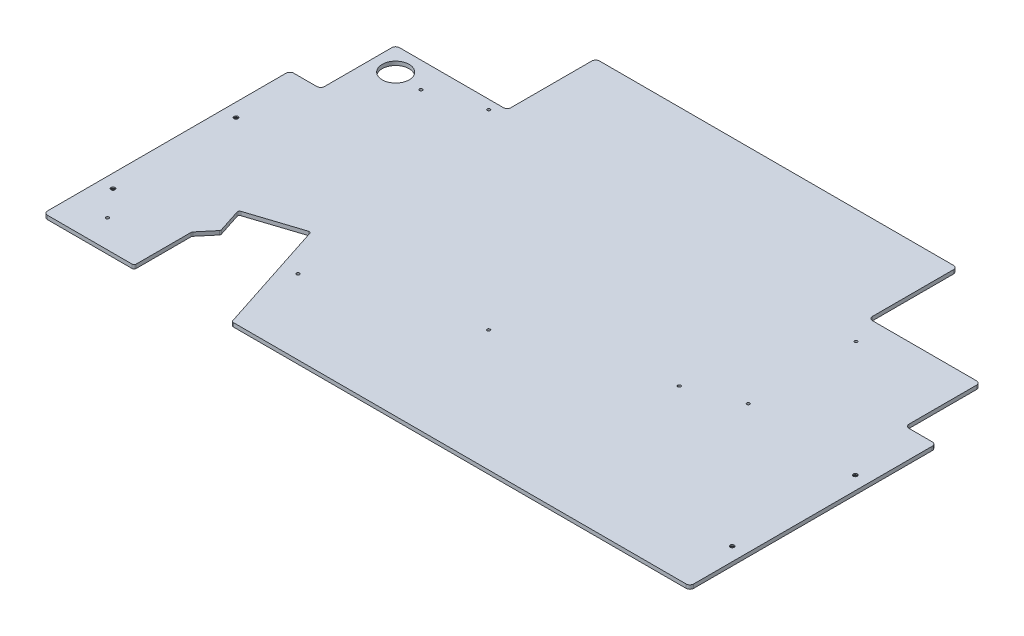
SolidWorks part; units mm, degrees
material "PE High Density"
ref_plane "Front Plane" through (0, 0, 0) normal (0, 0, 1) x (1, 0, 0)
ref_plane "Top Plane" through (0, 0, 0) normal (0, 1, 0) x (1, 0, 0)
ref_plane "Right Plane" through (0, 0, 0) normal (1, 0, 0) x (0, 0, -1)
sketch "Sketch1" plane through (0, 0, 0) normal (0, 1, 0) x (1, 0, 0)
  line L0 (1016, 406.4) -> (1066.8, 406.4)
  line L1 (0, 0) -> (1066.8, 0)
  line L2 (0, 0) -> (0, 406.4)
  line L3 (0, 406.4) -> (50.8, 406.4)
  line L4 (1066.8, 0) -> (1066.8, 406.4)
  line L6 (234.95, 530.225) -> (234.95, 676.275)
  line L7 (234.95, 676.275) -> (831.85, 676.275)
  line L8 (831.85, 530.225) -> (831.85, 676.275)
  line L12 (234.95, 530.225) -> (50.8, 530.225)
  line L13 (50.8, 406.4) -> (50.8, 530.225)
  line L16 (831.85, 530.225) -> (1016, 530.225)
  line L17 (1016, 406.4) -> (1016, 530.225)
  circle A2 centre (22.225, 92.075) radius 3.3734
  circle A3 centre (1044.575, 92.075) radius 3.3734
  circle A4 centre (22.225, 295.275) radius 3.3734
  circle A5 centre (1044.575, 295.275) radius 3.3734
  dimension "D16" = 92.075
  dimension "D11" = 6.7469
  dimension "D1" = 1066.8
  dimension "D2" = 406.4
  dimension "D3" = 596.9
  dimension "D4" = 234.95
  dimension "D5" = 676.275
  dimension "D6" = 50.8
  dimension "D7" = 50.8
  dimension "D8" = 146.05
  dimension "D9" = 146.05
  dimension "D10" = 203.2
  dimension "D15" = 22.225
  dimension "D18" = 22.225
extrude "Boss-Extrude1" add sketch "Sketch1" along normal blind 6.35
sketch "Sketch3" plane through (0, 6.35, 0) normal (0, 1, 0) x (1, 0, 0)
  line L0 (0, 0) -> (1066.8, 0) construction
  line L1 (0, 406.4) -> (0, 0) construction
  line L2 (234.95, 530.225) -> (50.8, 530.225) construction
  line L3 (50.8, 530.225) -> (50.8, 406.4) construction
  line L4 (59.3115, 45.8775) -> (771.914, 277.4161) construction
  line L5 (134.9375, 487.7489) -> (219.4864, 515.2205) construction
  line L6 (0, 406.4) -> (0, 0) construction
  circle A0 centre (134.9375, 487.7489) radius 2.4575
  circle A1 centre (219.4864, 515.2205) radius 2.4575
  circle A2 centre (59.3115, 45.8775) radius 2.4575
  circle A3 centre (296.8457, 123.057) radius 2.4574
  circle A4 centre (534.3799, 200.2365) radius 2.4575
  circle A5 centre (771.914, 277.4161) radius 2.4575
  circle A6 centre (854.075, 309.0545) radius 2.4575
  circle A7 centre (854.075, 486.8545) radius 2.4575
  circle A8 centre (88.9, 492.125) radius 22.225
  dimension "D6" = 486.8545
  dimension "D16" = 4.9149
  dimension "D17" = 44.45
  dimension "D1" = 45.8775
  dimension "D2" = 18
  dimension "D3" = 249.7582
  dimension "D4" = 249.7582
  dimension "D5" = 309.0545
  dimension "D7" = 59.3115
  dimension "D8" = 249.7582
  dimension "D9" = 88.9
  dimension "D10" = 396.875
  dimension "D11" = 854.075
  dimension "D12" = 134.9375
  dimension "D18" = 38.1
  dimension "D19" = 38.1
extrude "Cut-Extrude2" cut sketch "Sketch3" against normal through all
sketch "Sketch2" plane through (0, 6.35, 0) normal (0, 1, 0) x (1, 0, 0)
  line L0 (0, 0) -> (1066.8, 0) construction
  line L1 (310.5788, 0) -> (149.225, 0)
  line L4 (149.225, 0) -> (149.225, 95.25)
  line L5 (310.5788, 0) -> (247.65, 193.675)
  line L6 (247.65, 193.675) -> (157.0619, 164.2411)
  line L8 (0, 406.4) -> (0, 0) construction
  line L10 (157.0619, 164.2411) -> (171.0336, 121.2405)
  line L11 (171.0336, 121.2405) -> (149.225, 95.25)
  dimension "D1" = 247.65
  dimension "D2" = 149.225
  dimension "D3" = 72
  dimension "D4" = 122
  dimension "D5" = 95.25
  dimension "D6" = 193.675
  dimension "D8" = 95.25
extrude "Cut-Extrude1" cut sketch "Sketch2" against normal through all
sketch "Sketch4" plane through (0, 0, 0) normal (0, 1, 0) x (1, 0, 0)
  point P0 (22.225, 92.075)
  point P4 (22.225, 295.275)
  point P5 (1044.575, 92.075)
  point P6 (1044.575, 295.275)
hole_wizard "CSK for 1/4 Flat Head Machine Screw1" positions "3DSketch1" profile "Sketch5" countersink size "1/4" standard "ANSI Inch" end condition through all
sketch3d "3DSketch1"
  line L0 (22.225, 6.35, -295.275) -> (22.225, 0, -295.275) construction
  line L1 (1044.575, 6.35, -295.275) -> (1044.575, 0, -295.275) construction
  point P0 (22.225, 0, -92.075)
  point P9 (1044.575, 0, -92.075)
  point P24 (22.225, 0, -295.275)
  point P28 (1044.575, 0, -295.275)
sketch "Sketch5" plane through (22.225, 0, -92.075) normal (1, 0, 0) x (0, 0, -1)
  line L0 (0, 0) -> (0, 6.35)
  line L1 (0, 6.35) -> (3.3782, 6.35)
  line L2 (3.3782, 6.35) -> (3.3782, 4.5369)
  line L3 (3.3782, 4.5369) -> (6.4389, 1.016)
  line L4 (6.4389, 1.016) -> (6.4389, 0)
  line L6 (6.4389, 0) -> (0, 0)
  line L7 (-3.3782, 4.5369) -> (-6.4389, 1.016) construction
  line L11 (0, -6.35) -> (0, 107.95) construction
  dimension "Thru Hole Dia." = 6.7564
  dimension "Thru Hole Depth" = 6.35
  dimension "C'Sink Dia." = 12.8778
  dimension "C'Sink Angle" = 82
  dimension "Head Clearance" = 1.016
fillet "Fillet1" radius 6.35 12 edges at (50.8, 3.175, -406.4) (0, 3.175, -406.4) (50.8, 3.175, -530.225) (234.95, 3.175, -530.225) (234.95, 3.175, -676.275) (0, 3.175, 0) (1066.8, 3.175, 0) (1066.8, 3.175, -406.4) (1016, 3.175, -406.4) (1016, 3.175, -530.225) (831.85, 3.175, -530.225) (831.85, 3.175, -676.275)
fillet "Fillet3" radius 3.175 6 edges at (310.5788, 3.175, 0) (247.65, 3.175, -193.675) (157.0619, 3.175, -164.2411) (171.0336, 3.175, -121.2405) (149.225, 3.175, -95.25) (149.225, 3.175, 0)
